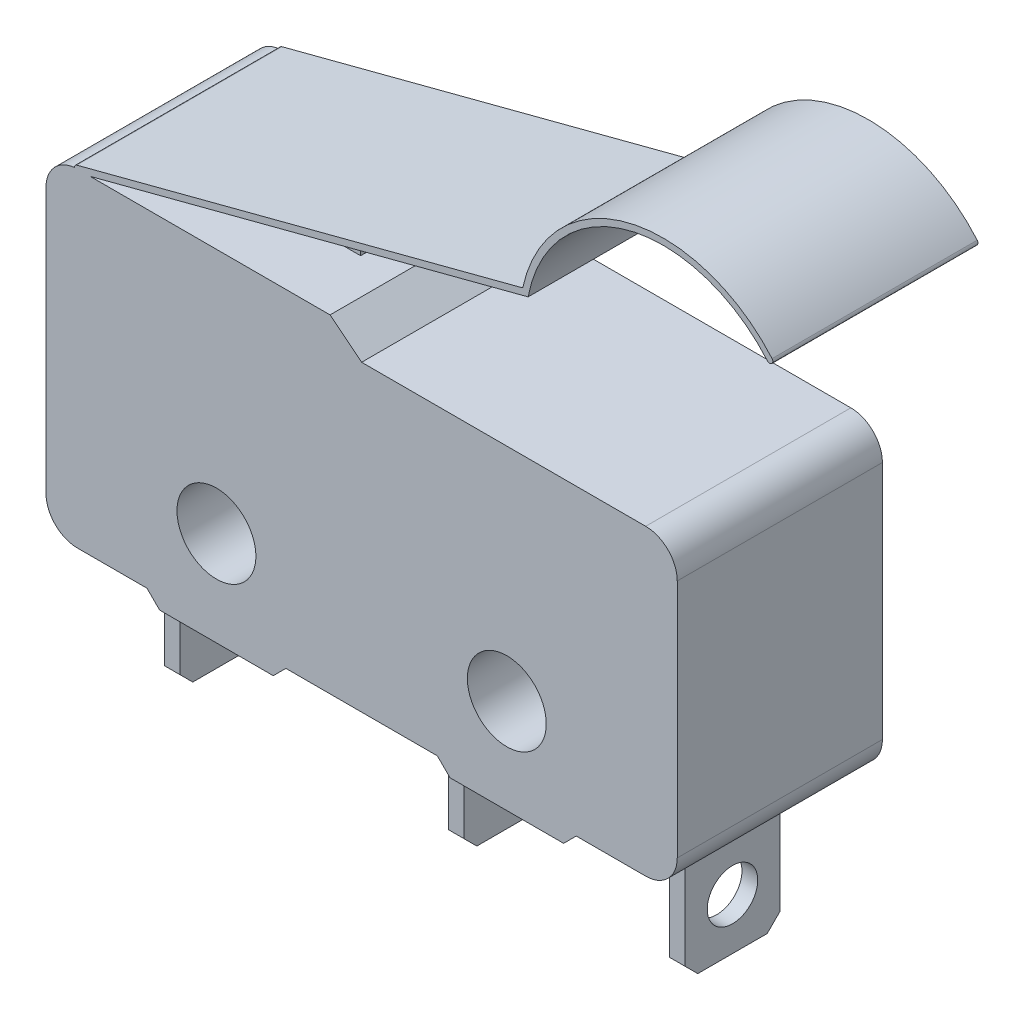
SolidWorks part; units mm, degrees
ref_plane "Front Plane" through (0, 0, 0) normal (0, 0, 1) x (1, 0, 0)
ref_plane "Top Plane" through (0, 0, 0) normal (0, 1, 0) x (1, 0, 0)
ref_plane "Right Plane" through (0, 0, 0) normal (1, 0, 0) x (0, 0, -1)
sketch "Sketch2" plane through (0, 0, 0) normal (0, 0, 1) x (1, 0, 0)
  line L0 (0, 9.8) -> (0, 1.4)
  line L1 (0, -55) -> (0, 55) construction
  line L2 (1, 10.8) -> (9, 10.8)
  line L3 (3.6, 0) -> (7.2, 0)
  line L5 (20, 1.4) -> (20, 9)
  line L6 (19, 10) -> (10, 10)
  line L7 (10, 10) -> (9, 10.8)
  line L8 (12.8, 0) -> (16.4, 0)
  line L9 (19, 0.4) -> (16.4, 0.4)
  line L10 (16.4, 0.4) -> (16.4, 0)
  line L11 (16.4, 0) -> (12.8, 0)
  line L12 (12.8, 0) -> (12.8, 0.4)
  line L13 (12.8, 0.4) -> (7.2, 0.4)
  line L14 (3.6, 0.4) -> (1, 0.4)
  line L15 (7.2, 0) -> (7.2, 0.4)
  line L16 (3.6, 0) -> (7.2, 0)
  line L17 (3.6, 0.4) -> (3.6, 0)
  arc A0 (1, 0.4) -> (0, 1.4) centre (1, 1.4) cw
  arc A1 (20, 1.4) -> (19, 0.4) centre (19, 1.4) cw
  arc A2 (20, 9) -> (19, 10) centre (19, 9) ccw
  arc A3 (0, 9.8) -> (1, 10.8) centre (1, 9.8) cw
  circle A4 centre (5.4, 3) radius 1.25
  circle A5 centre (14.6, 3) radius 1.25
  point P25 (0, 10.8)
  dimension "D2" = 1
  dimension "D1" = 3.6
extrude "Boss-Extrude1" add sketch "Sketch2" along normal blind 6.5 contours A3 L0 A0 L14 L17 L3 L15 L13 L12 L8 L10 L9 A1 L5 A2 L6 L7 L2 A5 A4 region at (9.7921, 5.4424, 0)
chamfer "Chamfer1" distance 0.4 angle 45 4 edges at (3.6, 0.4, 3.25) (7.2, 0.4, 3.25) (12.8, 0.4, 3.25) (16.4, 0.4, 3.25)
sketch "Sketch3" plane through (0, 10.8, 0) normal (0, 1, 0) x (1, 0, 0)
  line L3 (5.8616, -4.3931) -> (7.8616, -4.3931)
  line L4 (5.8616, -4.3931) -> (5.8616, -2.3931)
  line L5 (5.8616, -2.3931) -> (7.8616, -2.3931)
  line L6 (7.8616, -4.3931) -> (7.8616, -2.3931)
  line L7 (5.8616, -4.3931) -> (7.8616, -2.3931) construction
  line L8 (5.8616, -2.3931) -> (7.8616, -4.3931) construction
  dimension "D1" = 2
  dimension "D2" = 2
extrude "Boss-Extrude2" add sketch "Sketch3" along normal blind 1.5
fillet "Fillet1" radius 1 2 edges at (5.8616, 12.3, 3.3931) (7.8616, 12.3, 3.3931)
sketch "Sketch4" plane through (0, 0.4, 0) normal (0, -1, 0) x (1, 0, 0)
  line L2 (2, 3.25) -> (2, 4.75)
  line L3 (2, 4.75) -> (2.5, 4.75)
  line L4 (2.5, 4.75) -> (2.5, 1.75)
  line L5 (2.5, 1.75) -> (2.0379, 1.75)
  line L6 (2.0379, 1.75) -> (2, 3.25)
  line L7 (11, 3.25) -> (11, 4.75)
  line L8 (11, 4.75) -> (11.5, 4.75)
  line L9 (11.5, 4.75) -> (11.5, 1.75)
  line L10 (11.5, 1.75) -> (11, 1.75)
  line L11 (11, 1.75) -> (11, 3.25)
  line L12 (18, 3.25) -> (18, 4.75)
  line L13 (18, 4.75) -> (18.5, 4.75)
  line L14 (18.5, 4.75) -> (18.5, 1.75)
  line L15 (18.5, 1.75) -> (18, 1.75)
  line L16 (18, 1.75) -> (18, 3.25)
extrude "Boss-Extrude3" add sketch "Sketch4" along normal blind 4
chamfer "Chamfer2" distance 0.4 angle 45 6 edges at (2.25, -3.6, 4.75) (18.25, -3.6, 4.75) (11.25, -3.6, 4.75) (2.2689, -3.6, 1.75) (18.25, -3.6, 1.75) (11.25, -3.6, 1.75)
sketch "Sketch5" plane through (18.5, 0, 0) normal (1, 0, 0) x (0, 0, -1)
  circle A0 centre (-3.25, -1.9831) radius 0.8
extrude "Cut-Extrude2" cut sketch "Sketch5" against normal blind 18
sketch "Sketch6" plane through (0, 0, 0) normal (0, 0, -1) x (-1, 0, 0)
  text T0 "5A250VAC" font "Century Gothic" height in points 8
extrude "Boss-Extrude4" add sketch "Sketch6" along normal blind 0.1
sketch "Esboço1" plane through (0, 0, 6.5) normal (0, 0, 1) x (1, 0, 0)
  line L0 (1, 10.8) -> (15.1892, 14.5125)
  line L1 (15.1892, 14.5125) -> (22.9287, 16.5375) construction
  line L2 (19.5525, 13.6385) -> (18.4261, 17.9436) construction
  line L3 (1.0253, 10.7033) -> (15.2755, 14.4317)
  line L4 (0.9747, 10.8967) -> (15.1039, 14.5936)
  arc A0 (22.9287, 16.5375) -> (15.1892, 14.5125) centre (19.5525, 13.6385) ccw
  arc A1 (6.8616, 12.3) -> (5.8616, 11.3) centre (6.8616, 11.3) ccw construction
  arc A2 (22.8528, 16.4724) -> (15.2755, 14.4317) centre (19.5525, 13.6385) ccw
  arc A3 (23.0045, 16.6027) -> (15.1039, 14.5936) centre (19.5525, 13.6385) ccw
  arc A4 (1.0253, 10.7033) -> (0.9747, 10.8967) centre (1, 10.8) cw
  arc A5 (22.8528, 16.4724) -> (23.0045, 16.6027) centre (22.9287, 16.5375) ccw
  dimension "D2" = 8
  dimension "D1" = 2.5
  dimension "D3" = 0.1
  dimension "D4" = 0.1
extrude "Ressalto-extrusão1" add sketch "Esboço1" against normal up to surface (6.5 mm away) contours A2 A5 A3 L4 A4 L3 | A3 L4 A4 L3 A2 A5 region at (1.1975, 10.8233, 6.5) up to face at (2.9329, 7.0158, 0)
